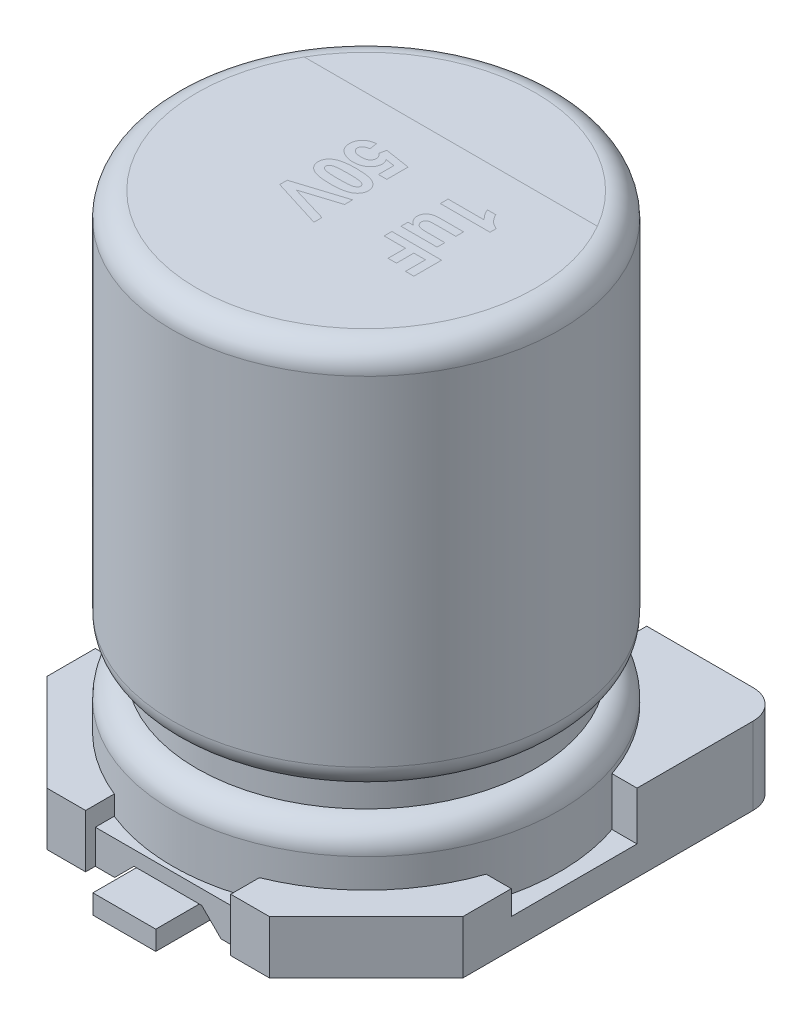
SolidWorks part; units mm, degrees
ref_plane "Front Plane" through (0, 0, 0) normal (0, 0, 1) x (1, 0, 0)
ref_plane "Top Plane" through (0, 0, 0) normal (0, 1, 0) x (1, 0, 0)
ref_plane "Right Plane" through (0, 0, 0) normal (1, 0, 0) x (0, 0, -1)
sketch "Sketch4" plane through (0, 0, 0) normal (0, 1, 0) x (1, 0, 0)
  circle A0 centre (0, 0) radius 2
  dimension "D1" = 4
extrude "Boss-Extrude2" add sketch "Sketch4" along normal blind 4
sketch "PIC" plane through (0, 0, 0) normal (0, 0, 1) x (1, 0, 0)
  line L0 (-219.571, 103.1632) -> (-235.4387, 557.5529) construction
sketch "Sketch6" plane through (0, 0, 0) normal (0, -1, 0) x (1, 0, 0)
  circle A0 centre (0, 0) radius 1.75
  dimension "D1" = 3.5
extrude "Boss-Extrude3" add sketch "Sketch6" along normal blind 0.3
sketch "Sketch7" plane through (0, -0.3, 0) normal (0, -1, 0) x (1, 0, 0)
  circle A0 centre (0, 0) radius 2
  dimension "D1" = 4
extrude "Boss-Extrude4" add sketch "Sketch7" along normal blind 0.8
fillet "Fillet2" radius 0.25 3 edges at (0, 0, 2) (0, 4, 2) (0, -0.3, -2)
ref_plane "Plane1" through (0, -1.4, 0) normal (0, 1, 0) x (1, 0, 0)
sketch "Sketch8" plane through (0, -1.4, 0) normal (0, 1, 0) x (1, 0, 0)
  line L1 (-2.15, 2.15) -> (2.15, 2.15)
  line L2 (-2.15, 2.15) -> (-2.15, -2.15)
  line L3 (-2.15, -2.15) -> (2.15, -2.15)
  line L4 (2.15, 2.15) -> (2.15, -2.15)
  line L5 (-2.15, 2.15) -> (2.15, -2.15) construction
  line L6 (-2.15, -2.15) -> (2.15, 2.15) construction
  point P0 (0, 0)
  dimension "D1" = 4.3
  dimension "D2" = 4.3
extrude "Boss-Extrude5" add sketch "Sketch8" along normal blind 0.8 separate body
sketch "Sketch9" plane through (0, -0.6, 0) normal (0, 1, 0) x (1, 0, 0)
  circle A0 centre (0, 0) radius 2
  dimension "D1" = 4
extrude "Cut-Extrude1" cut sketch "Sketch9" against normal blind 0.5
sketch "Sketch11" plane through (2.15, 0, 0) normal (1, 0, 0) x (0, 0, -1)
  line L0 (-2.15, -0.85) -> (-0.65, -0.85)
  line L1 (-2.15, -0.6) -> (-2.15, -1.4) construction
  line L2 (-0.65, -0.85) -> (-0.65, -1.1)
  line L3 (-0.65, -1.1) -> (0.65, -1.1)
  line L4 (0.65, -1.1) -> (0.65, -0.6)
  line L5 (-2.15, -0.6) -> (2.15, -0.6) construction
  line L6 (0.65, -0.6) -> (-2.15, -0.6)
  line L7 (-2.15, -0.6) -> (-2.15, -0.85)
  line L8 (0, 0) -> (0, -1.4) construction
  line L9 (-2.15, -1.4) -> (2.15, -1.4) construction
  dimension "D1" = 0.25
  dimension "D2" = 1.3
  dimension "D3" = 0.25
extrude "Cut-Extrude2" cut sketch "Sketch11" against normal through all
sketch "Sketch12" plane through (0, -1.4, 0) normal (0, -1, 0) x (1, 0, 0)
  line L0 (0, 2.15) -> (0, -2.15) construction
  line L1 (-2.15, 2.15) -> (2.15, 2.15) construction
  line L2 (2.15, -2.15) -> (-2.15, -2.15) construction
  line L3 (0, 0) -> (2.15, 0) construction
  line L4 (2.15, 2.15) -> (2.15, -2.15) construction
  line L5 (0.35, -0.85) -> (0.35, -2.5)
  line L7 (-0.35, 0.85) -> (-0.35, 2.5)
  line L8 (-0.35, 2.5) -> (0.35, 2.5)
  line L9 (0.35, 0.85) -> (0.35, 2.5)
  line L10 (-0.35, -2.5) -> (0.35, -2.5)
  line L11 (-0.35, -0.85) -> (-0.35, -2.5)
  arc A0 (-0.35, 0.85) -> (0.35, 0.85) centre (0, 0.85) ccw
  arc A1 (-0.35, -0.85) -> (0.35, -0.85) centre (0, -0.85) cw
  point P15 (0, 0.5)
  dimension "D1" = 0.35
  dimension "D2" = 1
  dimension "D3" = 0.7
extrude "Cut-Extrude3" cut sketch "Sketch12" against normal blind 0.2
sketch "Sketch17" plane through (0, -1.4, 0) normal (0, -1, 0) x (1, 0, 0)
  line L0 (0.35, 2.15) -> (-0.35, 2.15) construction
  line L1 (-0.75, 2.05) -> (0.75, 2.05)
  line L2 (-0.75, 2.05) -> (-0.75, 2.25)
  line L3 (-0.75, 2.25) -> (0.75, 2.25)
  line L4 (0.75, 2.05) -> (0.75, 2.25)
  line L5 (-0.75, 2.05) -> (0.75, 2.25) construction
  line L6 (-0.75, 2.25) -> (0.75, 2.05) construction
  line L7 (0, 0) -> (2.15, 0) construction
  line L8 (2.15, 2.15) -> (2.15, -2.15) construction
  line L9 (-0.75, -2.25) -> (0.75, -2.05) construction
  line L10 (-0.75, -2.05) -> (0.75, -2.25) construction
  line L11 (0.75, -2.05) -> (0.75, -2.25)
  line L12 (-0.75, -2.25) -> (0.75, -2.25)
  line L13 (-0.75, -2.05) -> (-0.75, -2.25)
  line L14 (-0.75, -2.05) -> (0.75, -2.05)
  point P0 (0, 2.15)
  point P16 (0, -2.15)
  dimension "D1" = 0.2
  dimension "D2" = 1.5
extrude "Cut-Extrude8" cut sketch "Sketch17" along direction (0, 1, 0) on the side against the normal blind 0.8
sketch "Sketch19" plane through (0, 0, 2.05) normal (0, 0, 1) x (1, 0, 0)
  line L0 (-0.75, -0.85) -> (-0.75, -1.4) construction
  line L1 (-0.75, -1.05) -> (0.75, -1.05)
  line L2 (-0.75, -1.05) -> (-0.75, -0.25)
  line L3 (-0.75, -0.25) -> (0.75, -0.25)
  line L4 (0.75, -1.05) -> (0.75, -0.25)
  line L5 (0.75, -0.85) -> (0.75, -1.4) construction
  line L6 (-0.75, -0.85) -> (0.75, -0.85) construction
  dimension "D1" = 0.2
  dimension "D2" = 0.8
extrude "Cut-Extrude10" cut sketch "Sketch19" against normal through all
sketch "Sketch13" plane through (0, -1.2, 0) normal (0, -1, 0) x (1, 0, 0)
  line L0 (-0.325, 2.5) -> (-0.325, 1.025)
  line L1 (0.325, 2.5) -> (0.325, 1.025)
  line L2 (-0.325, 2.5) -> (0.325, 2.5)
  line L3 (0, 0) -> (2.15, 0) construction
  line L4 (2.15, 2.15) -> (2.15, -2.15) construction
  line L5 (0, 0) -> (0, 2.15) construction
  line L6 (0.35, 2.15) -> (-0.35, 2.15) construction
  line L7 (0.75, 2.15) -> (2.15, 2.15) construction
  line L8 (-0.325, -2.5) -> (0.325, -2.5)
  line L9 (0.325, -2.5) -> (0.325, -1.025)
  line L10 (-0.325, -2.5) -> (-0.325, -1.025)
  arc A0 (-0.325, 1.025) -> (0.325, 1.025) centre (0, 1.025) ccw
  arc A1 (-0.325, -1.025) -> (0.325, -1.025) centre (0, -1.025) cw
  dimension "D1" = 1.475
  dimension "D2" = 0.65
  dimension "D3" = 0.35
extrude "Boss-Extrude6" add sketch "Sketch13" along normal blind 0.2 separate body
chamfer "Chamfer1" distance 1 angle 45 2 edges at (-2.15, -1.125, 2.15) (2.15, -1.125, 2.15)
chamfer "Chamfer2" distance 0.2 angle 45 6 edges at (0.35, -1.4, -1.45) (-0.35, -1.4, -1.45) (0, -1.4, -0.5) (-0.35, -1.4, 1.45) (0.35, -1.4, 1.45) (0, -1.4, 0.5)
sketch "Sketch18" plane through (0, -1.4, 0) normal (0, -1, 0) x (1, 0, 0)
  line L1 (-1.4, -1.4) -> (1.4, -1.4) construction
  line L2 (-1.4, -1.4) -> (-1.4, 1.4) construction
  line L3 (-1.4, 1.4) -> (1.4, 1.4) construction
  line L4 (1.4, -1.4) -> (1.4, 1.4) construction
  line L5 (-1.4, -1.4) -> (1.4, 1.4) construction
  line L6 (-1.4, 1.4) -> (1.4, -1.4) construction
  circle A0 centre (1.4, 1.4) radius 0.1
  circle A1 centre (1.4, -1.4) radius 0.1
  circle A2 centre (-1.4, -1.4) radius 0.1
  circle A3 centre (-1.4, 1.4) radius 0.1
  point P0 (0, 0)
  point P16 (0, 0)
  dimension "D2" = 0.2
  dimension "D1" = 2.8
  dimension "D3" = 4
extrude "Cut-Extrude9" cut sketch "Sketch18" against normal blind 0.05
sketch "Sketch15" plane through (0, 4, 0) normal (0, 1, 0) x (1, 0, 0)
  line L1 (0, 0) -> (0, 1.75) construction
  line L2 (-1.5155, 0.875) -> (1.5155, 0.875)
  arc A1 (1.5155, 0.875) -> (-1.5155, 0.875) centre (0, 0) ccw
  circle A2 centre (0, 0) radius 1.75 construction
  dimension "D1" = 0.875
wrap "Wrap1" sketch "Sketch15" wrap type scribe source sketch "Sketch15" face at (0, 4, 1.75)
sketch "Sketch16" plane through (0, 4, 0) normal (0, 1, 0) x (1, 0, 0)
  line L0 (0.5, 0.5) -> (0.5, -0.5) construction
  line L1 (-0.5, 0.5) -> (-0.5, -0.5) construction
  text T0 "<b>1uF</b>" font "Arial Narrow" height in points 2
  text T1 "<b>50V   </b>" font "Arial Narrow" height in points 2
  dimension "D1" = 0.5
  dimension "D2" = 0.5
  dimension "D3" = 0.5
  dimension "D4" = 1
wrap "Wrap2" sketch "Sketch16" wrap type scribe source sketch "Sketch16" face at (0, 4, 0.4375)
fillet "Fillet3" radius 0.3 2 edges at (2.15, -1, -2.15) (-2.15, -1, -2.15)
